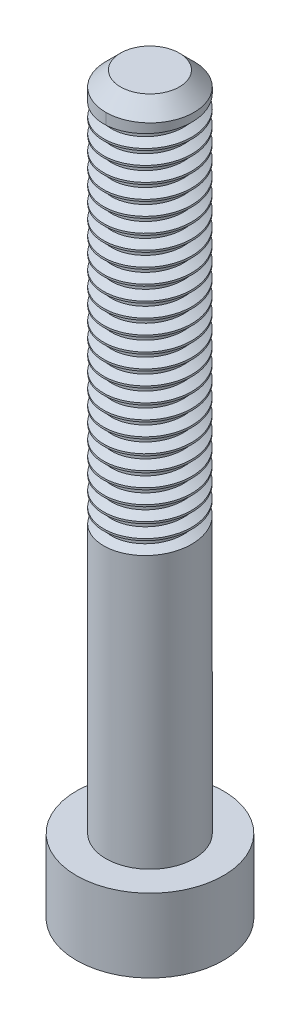
SolidWorks part; units mm, degrees
material "AISI 304"
ref_plane "Front Plane" through (0, 0, 0) normal (0, 0, 1) x (1, 0, 0)
ref_plane "Top Plane" through (0, 0, 0) normal (0, 1, 0) x (1, 0, 0)
ref_plane "Right Plane" through (0, 0, 0) normal (1, 0, 0) x (0, 0, -1)
sketch "Sketch2" plane through (0, 0, 0) normal (1, 0, 0) x (0, 0, -1)
  line L0 (0, 97.3351) -> (0, -84.2995) construction
  line L1 (0, 0) -> (-5, 0)
  line L2 (-5, 0) -> (-5, 5)
  line L3 (-5, 5) -> (-3, 5)
  line L4 (-3, 5) -> (-3, 50)
  line L5 (-3, 50) -> (0, 50)
  line L6 (0, 0) -> (0, 50)
  dimension "D1" = 50
  dimension "D2" = 5
  dimension "D3" = 3
  dimension "D4" = 5
revolve "Revolve1" add sketch "Sketch2" angle 360 about L0
chamfer "Chamfer1" distance 1 angle 45 1 edges at (0, 50, 3)
thread "Thread1" pitch 1 method cut profile "Thread Profile1" start angle 0, offset 0, length 25, pitch 1, diameter 6
ref_plane "Plane1" through (-3, 49, 0) normal (0, 0, 1) x (-1, 0, 0)
sketch "Thread Profile1" plane through (-3, 49, 0) normal (0, 0, 1) x (-1, 0, 0)
  line L0 (0, 0) -> (0, 1) construction
  line L11 (0, 0) -> (0, 0.875)
  line L12 (0, 0.875) -> (-0.5413, 0.5625)
  line L13 (-0.5413, 0.5625) -> (-0.5413, 0.3125)
  line L15 (-0.5413, 0.3125) -> (0, 0)
  line L17 (-0.5413, 0.4375) -> (0, 0.4375) construction
  point P2 (0, 0)
  dimension "Pitch" = 1
  dimension "Profile_Angle" = 60
  dimension "Profile_Land" = 0.25
  dimension "Profile_Height" = 0.5413
